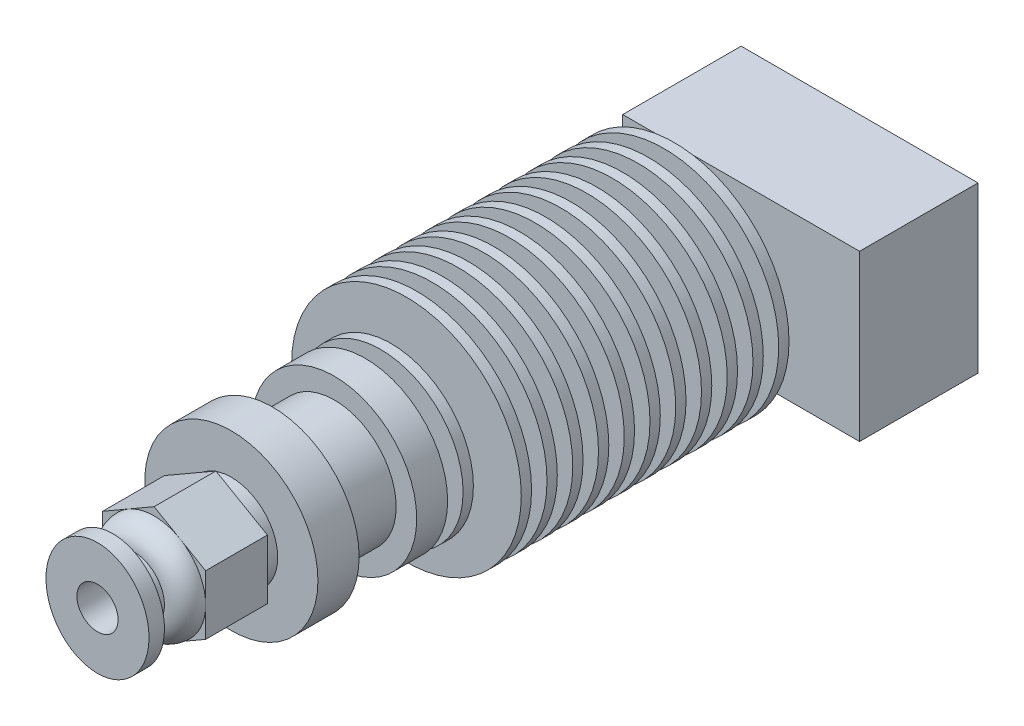
SolidWorks part; units mm, degrees
ref_plane "Спереди" through (0, 0, 0) normal (0, 0, 1) x (1, 0, 0)
ref_plane "Сверху" through (0, 0, 0) normal (0, 1, 0) x (1, 0, 0)
ref_plane "Справа" through (0, 0, 0) normal (1, 0, 0) x (0, 0, -1)
sketch "Эскиз1" plane through (0, 0, 0) normal (0, 0, 1) x (1, 0, 0)
  circle A0 centre (0, 0) radius 6
  dimension "D1" = 12
ref_plane "Плоскость1" through (0, 0, 26) normal (0, 0, 1) x (1, 0, 0)
sketch "Эскиз2" plane through (0, 0, 26) normal (0, 0, 1) x (1, 0, 0)
  circle A0 centre (0, 0) radius 4.25
  dimension "D1" = 8.5
loft "По сечениям1" add profiles "Эскиз2", "Эскиз1" connector at (3.249, 2.7398, 26) connector at (5.5618, 2.2507, 0)
sketch "Эскиз3" plane through (0, 0, 0) normal (0, 0, -1) x (-1, 0, 0)
  circle A0 centre (0, 0) radius 11.15
  dimension "D1" = 22.3
extrude "Бобышка-Вытянуть1" add sketch "Эскиз3" against normal blind 1
ref_axis "Ось1" through (0, 0, -80.9) along (0, 0, 1)
pattern_linear "Линейный массив1" count 11 spacing 2.5 along (0, 0, 1) of "Бобышка-Вытянуть1"
sketch "Эскиз4" plane through (0, 0, 26) normal (0, 0, 1) x (1, 0, 0)
  circle A2 centre (0, 0) radius 4.25
  circle A3 centre (0, 0) radius 4.25
  dimension "D1" = 0
extrude "Бобышка-Вытянуть2" add sketch "Эскиз4" along normal blind 1.5
sketch "Эскиз5" plane through (0, 0, 27.5) normal (0, 0, 1) x (1, 0, 0)
  circle A0 centre (0, 0) radius 8
  dimension "D1" = 16
extrude "Бобышка-Вытянуть3" add sketch "Эскиз5" along normal blind 1
sketch "Эскиз6" plane through (0, 0, 28.5) normal (0, 0, 1) x (1, 0, 0)
  circle A0 centre (0, 0) radius 4.25
  dimension "D1" = 8.5
extrude "Бобышка-Вытянуть4" add sketch "Эскиз6" along normal blind 1.5
sketch "Эскиз7" plane through (0, 0, 30) normal (0, 0, 1) x (1, 0, 0)
  circle A0 centre (0, 0) radius 8
  dimension "D1" = 16
extrude "Бобышка-Вытянуть5" add sketch "Эскиз7" along normal blind 3
sketch "Эскиз8" plane through (0, 0, 33) normal (0, 0, 1) x (1, 0, 0)
  circle A0 centre (0, 0) radius 6
  dimension "D1" = 12
extrude "Бобышка-Вытянуть6" add sketch "Эскиз8" along normal blind 6
sketch "Эскиз9" plane through (0, 0, 39) normal (0, 0, 1) x (1, 0, 0)
  circle A0 centre (0, 0) radius 8.4066
extrude "Бобышка-Вытянуть7" add sketch "Эскиз9" along normal blind 4
sketch "Эскиз10" plane through (0, 0, 0) normal (0, 0, -1) x (-1, 0, 0)
  circle A0 centre (0, 0) radius 2.5
  dimension "D1" = 5
extrude "Бобышка-Вытянуть8" add sketch "Эскиз10" along normal blind 3
sketch "Эскиз11" plane through (0, 0, -3) normal (0, 0, -1) x (-1, 0, 0)
  line L1 (-15, -8) -> (8, -8)
  line L2 (-15, -8) -> (-15, 8)
  line L3 (-15, 8) -> (8, 8)
  line L4 (8, -8) -> (8, 8)
  line L5 (-15, -8) -> (8, 8) construction
  line L6 (-15, 8) -> (8, -8) construction
  point P0 (-3.5, 0)
  dimension "D1" = 23
  dimension "D2" = 16
  dimension "D3" = 8
extrude "Бобышка-Вытянуть9" add sketch "Эскиз11" along normal blind 11.5
sketch "Эскиз12" plane through (0, 0, -14.5) normal (0, 0, -1) x (-1, 0, 0)
  line L1 (0, 4.0415) -> (-3.5, 2.0207)
  line L2 (-3.5, 2.0207) -> (-3.5, -2.0207)
  line L3 (-3.5, -2.0207) -> (0, -4.0415)
  line L4 (0, -4.0415) -> (3.5, -2.0207)
  line L5 (3.5, -2.0207) -> (3.5, 2.0207)
  line L6 (3.5, 2.0207) -> (0, 4.0415)
  circle A0 centre (0, 0) radius 3.5 construction
  dimension "D1" = 7
extrude "Бобышка-Вытянуть10" add sketch "Эскиз12" along normal blind 3
sketch "Эскиз13" plane through (0, 0, -17.5) normal (0, 0, -1) x (-1, 0, 0)
  circle A0 centre (0, 0) radius 2
  dimension "D1" = 4
extrude "Бобышка-Вытянуть11" add sketch "Эскиз13" along normal blind 2 draft 35
sketch "Эскиз14" plane through (0, 0, 43) normal (0, 0, 1) x (1, 0, 0)
  circle A0 centre (0, 0) radius 4.5
  dimension "D1" = 9
extrude "Бобышка-Вытянуть12" add sketch "Эскиз14" along normal blind 1.5
sketch "Эскиз15" plane through (0, 0, 44.5) normal (0, 0, 1) x (1, 0, 0)
  line L2 (0, 5.7735) -> (-5, 2.8868)
  line L3 (-5, 2.8868) -> (-5, -2.8868)
  line L4 (-5, -2.8868) -> (0, -5.7735)
  line L5 (0, -5.7735) -> (5, -2.8868)
  line L6 (5, -2.8868) -> (5, 2.8868)
  line L7 (5, 2.8868) -> (0, 5.7735)
  circle A0 centre (0, 0) radius 5 construction
  dimension "D1" = 10
extrude "Бобышка-Вытянуть13" add sketch "Эскиз15" along normal blind 6
sketch "Эскиз16" plane through (0, 0, 50.5) normal (0, 0, 1) x (1, 0, 0)
  line L0 (0, 5.7735) -> (-5, 2.8868) construction
  circle A0 centre (0, 0) radius 5
extrude "Бобышка-Вытянуть14" add sketch "Эскиз16" along normal blind 2
fillet "Скругление1" radius 2 1 edges at (5, 0, 52.5)
sketch "Эскиз17" plane through (0, 0, 52.5) normal (0, 0, 1) x (1, 0, 0)
  circle A0 centre (0, 0) radius 3
  circle A1 centre (0, 0) radius 3 construction
extrude "Бобышка-Вытянуть15" add sketch "Эскиз17" along normal blind 1
sketch "Эскиз18" plane through (0, 0, 53.5) normal (0, 0, 1) x (1, 0, 0)
  circle A0 centre (0, 0) radius 2.5
  dimension "D1" = 5
extrude "Бобышка-Вытянуть16" add sketch "Эскиз18" along normal blind 1
sketch "Эскиз19" plane through (0, 0, 54.5) normal (0, 0, 1) x (1, 0, 0)
  ellipse E0 centre (0, 0) end of major axis (0, -5.5) minor radius 5
  dimension "D1" = 11
  dimension "D2" = 10
extrude "Бобышка-Вытянуть17" add sketch "Эскиз19" along normal blind 1.5
sketch "Эскиз20" plane through (0, 0, 56) normal (0, 0, 1) x (1, 0, 0)
  circle A0 centre (0, 0) radius 2
  dimension "D1" = 4
extrude "Вырез-Вытянуть1" cut sketch "Эскиз20" against normal blind 60
